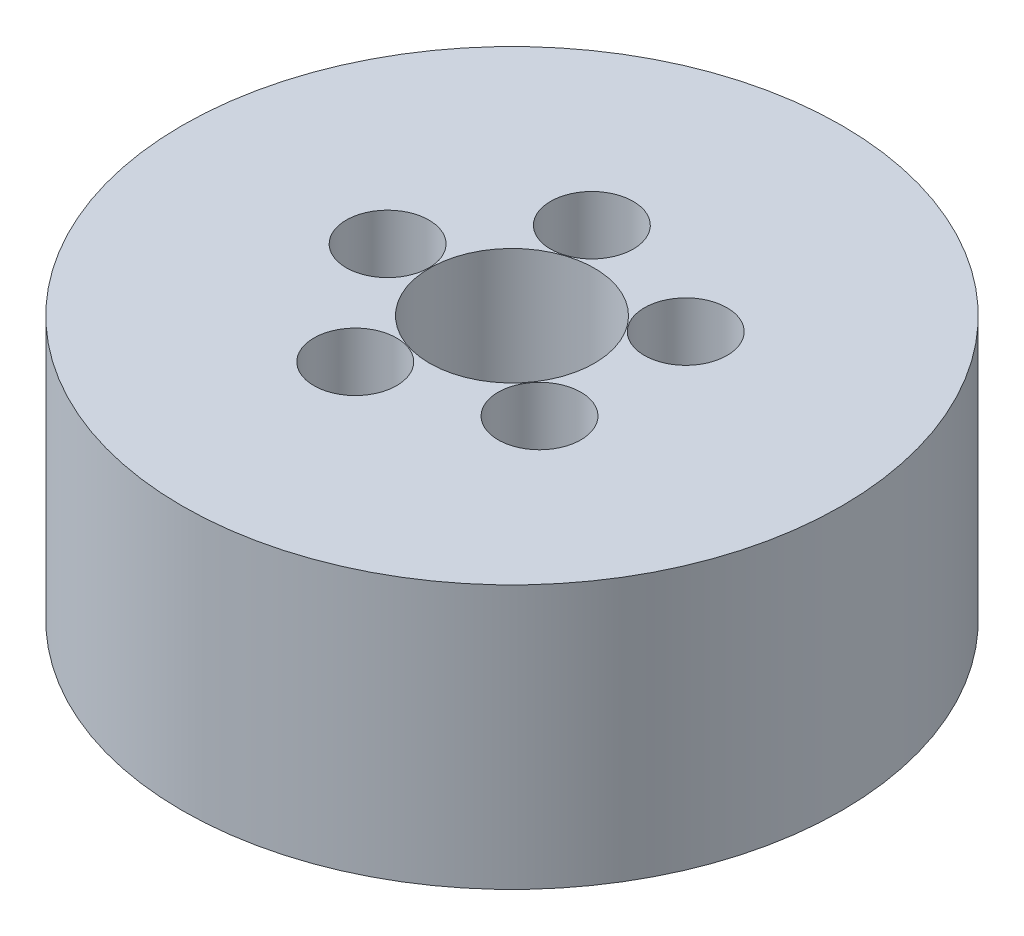
SolidWorks part; units mm, degrees
ref_plane "Front Plane" through (0, 0, 0) normal (0, 0, 1) x (1, 0, 0)
ref_plane "Top Plane" through (0, 0, 0) normal (0, 1, 0) x (1, 0, 0)
ref_plane "Right Plane" through (0, 0, 0) normal (1, 0, 0) x (0, 0, -1)
sketch "Sketch1" plane through (0, 0, 0) normal (0, 1, 0) x (1, 0, 0)
  circle A0 centre (0, 0) radius 20
  dimension "FLANGE_OD" = 40
extrude "Boss-Extrude1" add sketch "Sketch1" along normal blind 16
sketch "Sketch2" plane through (0, 0, 0) normal (0, 1, 0) x (1, 0, 0)
  circle A0 centre (0, 0) radius 5
  dimension "BORE_D" = 10
extrude "Cut-Extrude1" cut sketch "Sketch2" along normal through all
sketch "Sketch3" plane through (0, 16, 0) normal (0, 1, 0) x (1, 0, 0)
  circle A0 centre (0, 0) radius 7.5457 construction
  circle A1 centre (-7.5457, 0) radius 2.5087
  dimension "BOLT_D" = 5.0173
  dimension "BOLT_PCD" = 15.0915
extrude "Cut-Extrude2" cut sketch "Sketch3" against normal blind 12.1564
pattern_circular "CirPattern1" count 5 over 360 about axis through (0, 0, 0) along (0, 1, 0) of "Cut-Extrude2"
